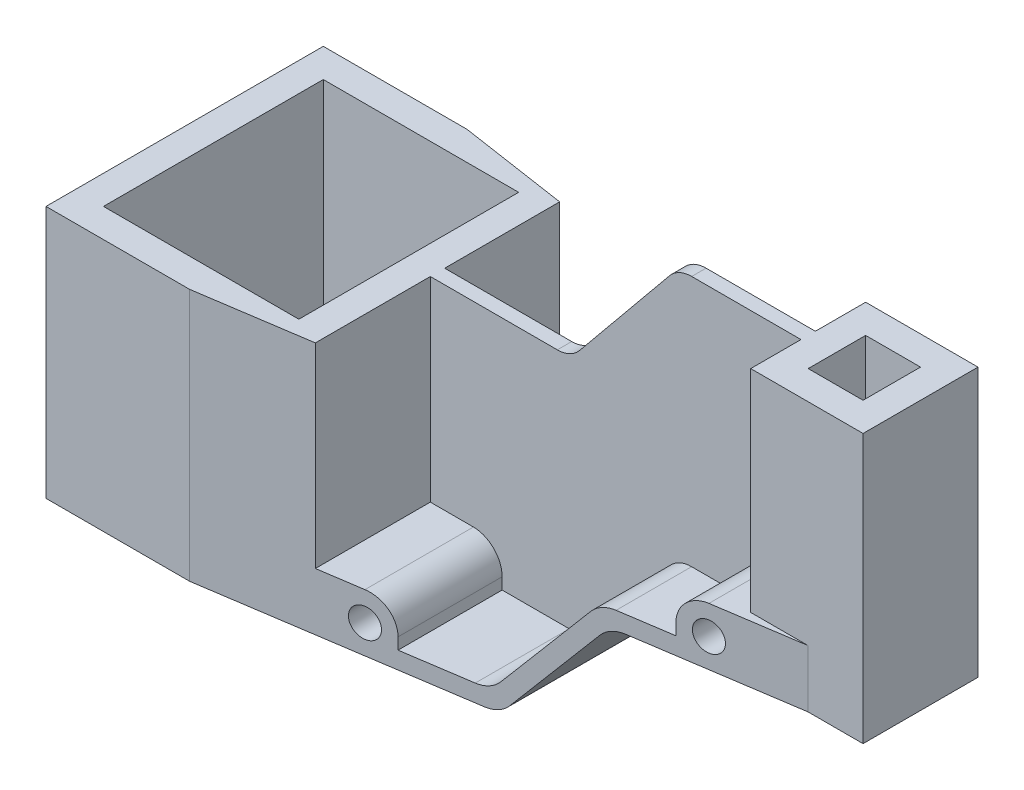
SolidWorks part; units mm, degrees
ref_plane "Front Plane" through (0, 0, 0) normal (0, 0, 1) x (1, 0, 0)
ref_plane "Top Plane" through (0, 0, 0) normal (0, 1, 0) x (1, 0, 0)
ref_plane "Right Plane" through (0, 0, 0) normal (1, 0, 0) x (0, 0, -1)
sketch "Sketch1" plane through (0, 0, 0) normal (0, 0, 1) x (1, 0, 0)
  line L2 (-55.5804, 93.4192) -> (200.5228, 93.4192)
  line L3 (-55.5804, 93.4192) -> (-55.5804, -40.0808)
  line L4 (-55.5804, -40.0808) -> (200.5228, -40.0808)
  line L5 (200.5228, 93.4192) -> (200.5228, -40.0808)
  circle A0 centre (150.5228, 9.9192) radius 5
extrude "Boss-Extrude1" add sketch "Sketch1" along normal mid plane 96.5 contours L3 L2 L5 L4
sketch "Sketch2" plane through (0, 0, 48.25) normal (0, 0, 1) x (1, 0, 0)
  line L0 (-55.5804, 93.4192) -> (-55.5804, -40.0808) construction
  line L7 (-55.5804, 93.4192) -> (32.4196, 93.4192)
  line L8 (-55.5804, 93.4192) -> (-55.5804, 47.9192)
  line L9 (-55.5804, 47.9192) -> (32.4196, 47.9192)
  line L10 (32.4196, 93.4192) -> (32.4196, 47.9192)
  circle A0 centre (151.4196, 9.9192) radius 5
extrude "Cut-Extrude1" cut sketch "Sketch2" against normal blind 96.5 contours L8 L7 L10 L9
sketch "Sketch4" plane through (0, 0, 48.25) normal (0, 0, 1) x (1, 0, 0)
  line L1 (200.5228, -40.0808) -> (161.4196, -40.0808)
  line L2 (200.5228, -40.0808) -> (200.5228, -0.0808)
  line L3 (200.5228, -0.0808) -> (161.4196, -0.0808)
  line L4 (161.4196, -40.0808) -> (161.4196, -0.0808)
extrude "Cut-Extrude2" cut sketch "Sketch4" against normal blind 96.5 contours L2 L1 L4 L3
sketch "Sketch5" plane through (0, 47.9192, 0) normal (0, 1, 0) x (1, 0, 0)
  line L8 (-45.5804, -38.25) -> (22.4196, -38.25)
  line L9 (22.4196, -38.25) -> (22.4196, 38.25)
  line L10 (22.4196, 38.25) -> (-45.5804, 38.25)
  line L11 (-45.5804, 38.25) -> (-45.5804, -38.25)
  line L12 (-45.5804, -38.25) -> (22.4196, -38.25)
  line L13 (22.4196, -38.25) -> (22.4196, 38.25)
  line L14 (22.4196, 38.25) -> (-45.5804, 38.25)
  line L15 (-45.5804, 38.25) -> (-45.5804, -38.25)
  dimension "D1" = 10
extrude "Cut-Extrude3" cut sketch "Sketch5" against normal blind 88
sketch "Sketch6" plane through (0, 93.4192, 0) normal (0, 1, 0) x (1, 0, 0)
  line L0 (200.5228, -48.25) -> (200.5228, 48.25) construction
  line L1 (200.5228, 48.25) -> (200.5228, 20)
  line L2 (-55.5804, -48.25) -> (32.4196, -48.25) construction
  line L7 (161.4196, 20) -> (161.4196, -20)
  line L8 (-11.5804, -48.25) -> (-5.5804, -48.25)
  line L12 (-55.5804, 48.25) -> (32.4196, 48.25) construction
  line L13 (-5.5804, 48.25) -> (-11.5804, 48.25)
  line L14 (200.5228, -48.25) -> (200.5228, -20)
  line L15 (200.5228, -20) -> (181.4196, -20)
  line L17 (32.4196, 48.25) -> (32.4196, 42.5094)
  line L19 (200.5228, -48.25) -> (32.4196, -48.25)
  line L20 (181.4196, 20) -> (200.5228, 20)
  line L21 (32.4196, -42.5094) -> (32.4196, -48.25)
  line L22 (200.5228, 48.25) -> (32.4196, 48.25)
  line L23 (181.4196, -20) -> (32.4196, -42.5094)
  line L24 (181.4196, 20) -> (32.4196, 42.5094)
extrude "Cut-Extrude4" cut sketch "Sketch6" against normal blind 133.5 contours L22 L17 L24 L20 L1 | L19 L21 L23 L15 L14
sketch "Sketch7" plane through (0, 47.9192, 0) normal (0, 1, 0) x (1, 0, 0)
  line L0 (-11.5804, 48.25) -> (-5.5804, 48.25)
  line L1 (-55.5804, 48.25) -> (32.4196, 48.25) construction
  line L2 (-5.5804, 48.25) -> (32.4196, 42.5094)
  line L3 (-5.5804, 48.25) -> (32.4196, 48.25)
  line L4 (32.4196, -42.5094) -> (-5.5804, -48.25)
  line L5 (-55.5804, -48.25) -> (32.4196, -48.25) construction
  line L6 (-5.5804, -48.25) -> (-11.5804, -48.25)
  line L7 (32.4196, 48.25) -> (32.4196, 42.5094)
  line L8 (-5.5804, -48.25) -> (32.4196, -48.25)
  line L9 (32.4196, -48.25) -> (32.4196, -42.5094)
extrude "Cut-Extrude5" cut sketch "Sketch7" against normal blind 88 contours L2 L7 L3
sketch "Sketch8" plane through (0, 47.9192, 0) normal (0, 1, 0) x (1, 0, 0)
  line L0 (-11.5804, -48.25) -> (-5.5804, -48.25)
  line L1 (-55.5804, -48.25) -> (32.4196, -48.25) construction
  line L2 (-5.5804, -48.25) -> (32.4196, -42.5094)
  line L3 (32.4196, -42.5094) -> (32.4196, -48.25)
  line L4 (32.4196, -48.25) -> (-5.5804, -48.25)
extrude "Cut-Extrude6" cut sketch "Sketch8" against normal blind 88 contours L2 L3 L4
sketch "Sketch9" plane through (0, 93.4192, 0) normal (0, 1, 0) x (1, 0, 0)
  line L0 (190.5228, 10) -> (190.5228, -10)
  line L1 (200.5228, 20) -> (161.4196, 20)
  line L2 (200.5228, 20) -> (200.5228, -20)
  line L3 (200.5228, -20) -> (161.4196, -20)
  line L4 (161.4196, 20) -> (161.4196, -20)
  line L5 (190.5228, -10) -> (171.4196, -10)
  line L6 (171.4196, 10) -> (171.4196, -10)
  line L7 (190.5228, 10) -> (171.4196, 10)
  dimension "D1" = 10
extrude "Cut-Extrude7" cut sketch "Sketch9" against normal blind 93.5 contours L0 L5 L6 L7
sketch "Sketch10" plane through (0, 93.4192, 0) normal (0, 1, 0) x (1, 0, 0)
  line L0 (161.4196, 20) -> (181.4196, 20)
  line L3 (181.4196, -20) -> (161.4196, -20)
  line L4 (161.4196, 20) -> (161.4196, -20)
  line L5 (181.4196, 20) -> (161.4196, 23.0214)
  line L6 (161.4196, 23.0214) -> (161.4196, 20)
  line L7 (181.4196, -20) -> (161.4196, -23.0214)
  line L8 (161.4196, -23.0214) -> (161.4196, -20)
extrude "Cut-Extrude8" cut sketch "Sketch10" against normal blind 73.5 contours L0 L5 L6 | L8 L7 L3
sketch "Sketch14" plane through (0, 93.4192, 0) normal (0, 1, 0) x (1, 0, 0)
  line L0 (161.4196, 20) -> (161.4196, 2.5)
  line L1 (161.4196, 2.5) -> (32.4196, 2.5)
  line L2 (161.4196, -20) -> (161.4196, -2.5)
  line L3 (32.4196, 42.5094) -> (32.4196, -42.5094) construction
  line L4 (32.4196, 2.5) -> (32.4196, 42.5094)
  line L5 (32.4196, -2.5) -> (161.4196, -2.5)
  line L6 (32.4196, 42.5094) -> (161.4196, 23.0214)
  line L7 (161.4196, 23.0214) -> (161.4196, 20)
  line L8 (32.4196, -2.5) -> (32.4196, -42.5094)
  line L9 (32.4196, -42.5094) -> (161.4196, -23.0214)
  line L10 (161.4196, -23.0214) -> (32.4196, -42.5094) construction
  line L11 (161.4196, -23.0214) -> (161.4196, -20)
extrude "Cut-Extrude9" cut sketch "Sketch14" against normal blind 45.5
sketch "Sketch17" plane through (161.4196, 0, 0) normal (1, 0, 0) x (0, 0, -1)
  line L1 (-23.0214, -0.0808) -> (23.0214, -0.0808)
  line L2 (-23.0214, -0.0808) -> (-23.0214, -40.0808)
  line L3 (-23.0214, -40.0808) -> (23.0214, -40.0808)
  line L4 (23.0214, -0.0808) -> (23.0214, -40.0808)
extrude "Cut-Extrude12" cut sketch "Sketch17" against normal blind 40
sketch "Sketch19" plane through (0, 47.9192, 0) normal (0, 1, 0) x (1, 0, 0)
  line L0 (32.4196, -2.5) -> (32.4196, -42.5094)
  line L1 (-5.5804, -48.25) -> (161.4196, -23.0214) construction
  line L2 (32.4196, -42.5094) -> (161.4196, -23.0214)
  line L3 (161.4196, -23.0214) -> (161.4196, -20)
  line L4 (161.4196, -20) -> (161.4196, -2.5)
  line L5 (161.4196, -2.5) -> (32.4196, -2.5) construction
  line L6 (161.4196, -20) -> (161.4196, -2.5) construction
  line L7 (161.4196, -2.5) -> (32.4196, -2.5)
  line L8 (32.4196, 2.5) -> (32.4196, 42.5094)
  line L9 (-5.5804, 48.25) -> (161.4196, 23.0214) construction
  line L10 (32.4196, 42.5094) -> (161.4196, 23.0214)
  line L11 (161.4196, 23.0214) -> (161.4196, 2.5)
  line L12 (32.4196, 2.5) -> (161.4196, 2.5) construction
  line L13 (32.4196, 2.5) -> (161.4196, 2.5) construction
  line L14 (161.4196, 2.5) -> (32.4196, 2.5)
extrude "Cut-Extrude13" cut sketch "Sketch19" against normal blind 28
sketch "Sketch23" plane through (0, 0, 23.0214) normal (0, 0, -1) x (-1, 0, 0)
  line L1 (-161.4196, -0.0808) -> (-121.4196, -0.0808)
  line L2 (-161.4196, -0.0808) -> (-161.4196, -40.0808)
  line L3 (-161.4196, -40.0808) -> (-121.4196, -40.0808)
  line L4 (-121.4196, -0.0808) -> (-121.4196, -40.0808)
extrude "Cut-Extrude20" cut sketch "Sketch23" against normal blind 8
sketch "Sketch24" plane through (0, 0, -23.0214) normal (0, 0, 1) x (1, 0, 0)
  line L1 (161.4196, -0.0808) -> (121.4196, -0.0808)
  line L2 (161.4196, -0.0808) -> (161.4196, -40.0808)
  line L3 (161.4196, -40.0808) -> (121.4196, -40.0808)
  line L4 (121.4196, -0.0808) -> (121.4196, -40.0808)
extrude "Cut-Extrude21" cut sketch "Sketch24" against normal blind 8
sketch "Sketch26" plane through (0, 19.9192, 0) normal (0, 1, 0) x (1, 0, 0)
  line L1 (161.4196, -2.5) -> (32.4196, -2.5) construction
  line L2 (141.4196, -2.5) -> (141.4196, -26.0428)
  line L3 (181.4196, -20) -> (32.4196, -42.5094) construction
  line L4 (141.4196, -26.0428) -> (32.4196, -42.5094)
  line L5 (32.4196, -42.5094) -> (32.4196, -2.5)
  line L6 (32.4196, -2.5) -> (141.4196, -2.5)
extrude "Cut-Extrude22" cut sketch "Sketch26" against normal blind 14 contours L2 L4 L5 L6
sketch "Sketch27" plane through (0, 19.9192, 0) normal (0, 1, 0) x (1, 0, 0)
  line L1 (32.4196, 2.5) -> (161.4196, 2.5) construction
  line L2 (141.4196, 2.5) -> (32.4196, 2.5)
  line L3 (32.4196, 2.5) -> (32.4196, 42.5094)
  line L4 (32.4196, 42.5094) -> (141.4196, 26.0428)
  line L5 (181.4196, 20) -> (32.4196, 42.5094) construction
  line L6 (141.4196, 26.0428) -> (141.4196, 2.5)
extrude "Cut-Extrude23" cut sketch "Sketch27" against normal blind 14
sketch "Sketch29" plane through (0, 0, 0) normal (0, 0, 1) x (1, 0, 0)
  circle A0 centre (151.4196, 9.9192) radius 5
extrude "Cut-Extrude24" cut sketch "Sketch29" against normal blind 30 and the other way blind 30
sketch "Sketch30" plane through (7.002, 0, 46.3492) normal (0.1494, 0, 0.9888) x (0.9888, 0, -0.1494)
  arc A1 (135.9429, 9.9192) -> (145.9429, 19.9192) centre (145.9429, 9.9192) cw
  point P11 (135.9429, 19.9192)
fillet "Fillet1" radius 10 1 edges at (141.4196, 19.9192, 14.2714)
sketch "Sketch31" plane through (0, 5.9192, 0) normal (0, 1, 0) x (1, 0, 0)
  line L0 (32.4196, -2.5) -> (57.4196, -2.5)
  line L1 (32.4196, -2.5) -> (141.4196, -2.5) construction
  line L2 (57.4196, -2.5) -> (57.4196, -38.7326)
  line L3 (141.4196, -26.0428) -> (32.4196, -42.5094) construction
  line L4 (57.4196, -38.7326) -> (32.4196, -42.5094)
  line L5 (32.4196, -42.5094) -> (32.4196, -2.5)
extrude "Cut-Extrude25" cut sketch "Sketch31" against normal blind 26
sketch "Sketch32" plane through (0, 5.9192, 0) normal (0, 1, 0) x (1, 0, 0)
  line L0 (32.4196, 2.5) -> (57.4196, 2.5)
  line L1 (32.4196, 2.5) -> (141.4196, 2.5) construction
  line L2 (57.4196, 2.5) -> (57.4196, 38.7326)
  line L3 (141.4196, 26.0428) -> (32.4196, 42.5094) construction
  line L4 (57.4196, 38.7326) -> (32.4196, 42.5094)
  line L5 (32.4196, 42.5094) -> (32.4196, 2.5)
extrude "Cut-Extrude26" cut sketch "Sketch32" against normal blind 26
sketch "Sketch35" plane through (7.002, 0, -46.3492) normal (0.1494, 0, -0.9888) x (-0.9888, 0, -0.1494)
  line L0 (-50.9897, -20.0808) -> (-50.9897, -34.0808)
  line L1 (-74.691, -34.0808) -> (-50.9897, -34.0808)
  line L3 (-112.7186, -3.653) -> (-85.1493, -36.5087)
  line L4 (-56.402, 5.9192) -> (-139.4595, 5.9192) construction
  line L5 (-109.9207, 2.347) -> (-82.3515, -30.5087)
  line L6 (-115.7159, -40.0808) -> (12.7251, -40.0808) construction
  arc A0 (-74.691, -34.0808) -> (-82.3515, -30.5087) centre (-74.691, -24.0808) cw
  arc A1 (-85.1493, -36.5087) -> (-77.4889, -40.0808) centre (-77.4889, -30.0808) ccw
  arc A2 (-112.7186, -3.653) -> (-120.379, -0.0808) centre (-120.379, -10.0808) ccw
  arc A3 (-109.9207, 2.347) -> (-117.5812, 5.9192) centre (-117.5812, -4.0808) ccw
  point P23 (-82.1519, -40.0808)
  point P26 (-115.7159, -0.0808)
  point P29 (-112.9181, 5.9192)
  dimension "D1" = 14
sketch "Sketch38" plane through (0, 0, 0) normal (0, 0, 1) x (1, 0, 0)
  line L4 (88.2322, -40.0808) -> (121.4196, -0.0808)
  point P12 (121.4196, -0.0808)
  point P14 (121.4196, -0.0808)
  point P16 (88.2322, -40.0808)
sketch "Sketch40" plane through (0, 5.9192, 0) normal (0, 1, 0) x (1, 0, 0)
  line L0 (57.4196, 38.7326) -> (81.3524, 35.1171)
  line L1 (81.3524, 35.1171) -> (81.3524, 2.5)
  line L2 (57.4196, 2.5) -> (141.4196, 2.5) construction
  line L3 (81.3524, 2.5) -> (57.4196, 2.5)
  line L4 (57.4196, 2.5) -> (57.4196, 38.7326)
extrude "Cut-Extrude28" cut sketch "Sketch40" against normal blind 40
sketch "Sketch41" plane through (0, 5.9192, 0) normal (0, 1, 0) x (1, 0, 0)
  line L0 (57.4196, -2.5) -> (57.4196, -38.7326)
  line L2 (57.4196, -2.5) -> (141.4196, -2.5) construction
  line L3 (81.3524, -2.5) -> (81.3524, -35.1171)
  line L4 (141.4196, -26.0428) -> (57.4196, -38.7326) construction
  line L6 (81.3524, -35.1171) -> (57.4196, -38.7326)
  line L7 (81.3524, -2.5) -> (57.4196, -2.5)
extrude "Cut-Extrude29" cut sketch "Sketch41" against normal blind 40
sketch "Sketch43" plane through (0, 0, 0) normal (0, 0, 1) x (1, 0, 0)
  line L0 (88.2322, -40.0808) -> (121.4196, -0.0808)
  line L1 (121.4196, -0.0808) -> (121.4196, -40.0808)
  line L2 (121.4196, -40.0808) -> (88.2322, -40.0808)
extrude "Cut-Extrude30" cut sketch "Sketch43" against normal blind 40 and the other way blind 40
fillet "Fillet2" radius 10 2 edges at (88.2322, -40.0808, 0) (121.4196, -0.0808, 0)
fillet "Fillet3" radius 10 1 edges at (57.4196, -20.0808, 20.6163)
fillet "Fillet4" radius 10 1 edges at (57.4196, -20.0808, -20.6163)
sketch "Sketch44" plane through (0, 0, 0) normal (0, 0, 1) x (1, 0, 0)
  line L0 (81.3524, 5.9192) -> (118.6532, 5.9192)
  line L1 (118.6532, 5.9192) -> (85.4657, -34.0808)
  line L2 (85.4657, -34.0808) -> (81.3524, -34.0808)
  line L3 (118.4559, -3.653) -> (91.1959, -36.5087) construction
  line L4 (81.3524, -34.0808) -> (81.3524, 5.9192)
extrude "Cut-Extrude31" cut sketch "Sketch44" against normal blind 40 and the other way blind 40
sketch "Sketch46" [suppressed] plane through (7.002, 0, 46.3492) normal (0.1494, 0, 0.9888) x (0.9888, 0, -0.1494)
  line L0 (75.1941, 5.9192) -> (112.8667, 5.9192)
  line L1 (79.3958, -34.0808) -> (75.1941, -34.0808)
  line L2 (135.9429, 5.9192) -> (112.9181, 5.9192) construction
  line L3 (112.8667, 5.9192) -> (79.3958, -34.0808)
  line L4 (75.1941, 5.9192) -> (75.1941, -34.0808)
sketch "Sketch49" plane through (0, 0, 0) normal (0, 0, 1) x (1, 0, 0)
  line L0 (118.6532, 5.9192) -> (118.6532, 93.4192)
  line L1 (161.4196, 93.4192) -> (32.4196, 93.4192) construction
  line L3 (32.4196, 93.4192) -> (32.4196, 47.9192)
  line L9 (81.3524, 5.9192) -> (118.6532, 5.9192)
  line L10 (118.6532, 93.4192) -> (32.4196, 93.4192)
  line L12 (32.4196, 47.9192) -> (81.3524, 47.9192)
  line L13 (81.3524, 47.9192) -> (81.3524, 5.9192)
extrude "Cut-Extrude32" cut sketch "Sketch49" against normal blind 2.5 and the other way blind 2.5
sketch "Sketch50" [suppressed] plane through (0, 0, 0) normal (0, 0, 1) x (1, 0, 0)
  line L1 (118.6532, 5.9192) -> (81.3524, 5.9192)
  line L2 (118.6532, 5.9192) -> (85.4657, -34.0808)
  line L3 (85.4657, -34.0808) -> (80.855, -34.0808)
  line L4 (80.855, -34.0808) -> (81.3524, 5.9192)
extrude "Boss-Extrude2" [suppressed] add sketch "Sketch50" along normal blind 2.5 and the other way blind 2.5
sketch "Sketch52" [suppressed] plane through (0, 0, 0) normal (0, 0, 1) x (1, 0, 0)
  line L0 (81.3524, 47.9192) -> (118.6532, 93.4192)
  line L1 (118.6532, 93.4192) -> (118.6532, 5.9192)
  line L2 (118.6532, 5.9192) -> (81.3524, 5.9192)
  line L3 (81.3524, 5.9192) -> (81.3524, 47.9192)
extrude "Boss-Extrude3" [suppressed] add sketch "Sketch52" along normal blind 2.5 and the other way blind 2.5
fillet "Fillet6" [suppressed] radius 10
sketch "Sketch53" plane through (0, 0, 0) normal (0, 0, 1) x (1, 0, 0)
  circle A0 centre (47.4196, -30.0808) radius 5
extrude "Cut-Extrude33" cut sketch "Sketch53" against normal blind 43 and the other way blind 43
sketch "Sketch55" plane through (0, 0, 0) normal (0, 0, 1) x (1, 0, 0)
  line L0 (81.3524, 47.9192) -> (118.6532, 93.4192)
  line L1 (118.6532, 93.4192) -> (118.6532, 5.9192)
  line L2 (118.6532, 5.9192) -> (85.4657, -34.0808)
  line L3 (85.4657, -34.0808) -> (80.855, -34.0808)
  line L4 (80.855, -34.0808) -> (81.3524, 47.9192)
extrude "Boss-Extrude4" add sketch "Sketch55" along normal blind 2.5 and the other way blind 2.5
fillet "Fillet7" radius 10 7 edges at (85.4657, -34.0808, -18.4979) (118.6532, 5.9192, -15.991) (141.4196, 19.9192, -14.2714) (81.3524, 47.9192, 0) (118.6532, 93.4192, 0) (85.4657, -34.0808, 18.4979) (118.6532, 5.9192, 15.991)
